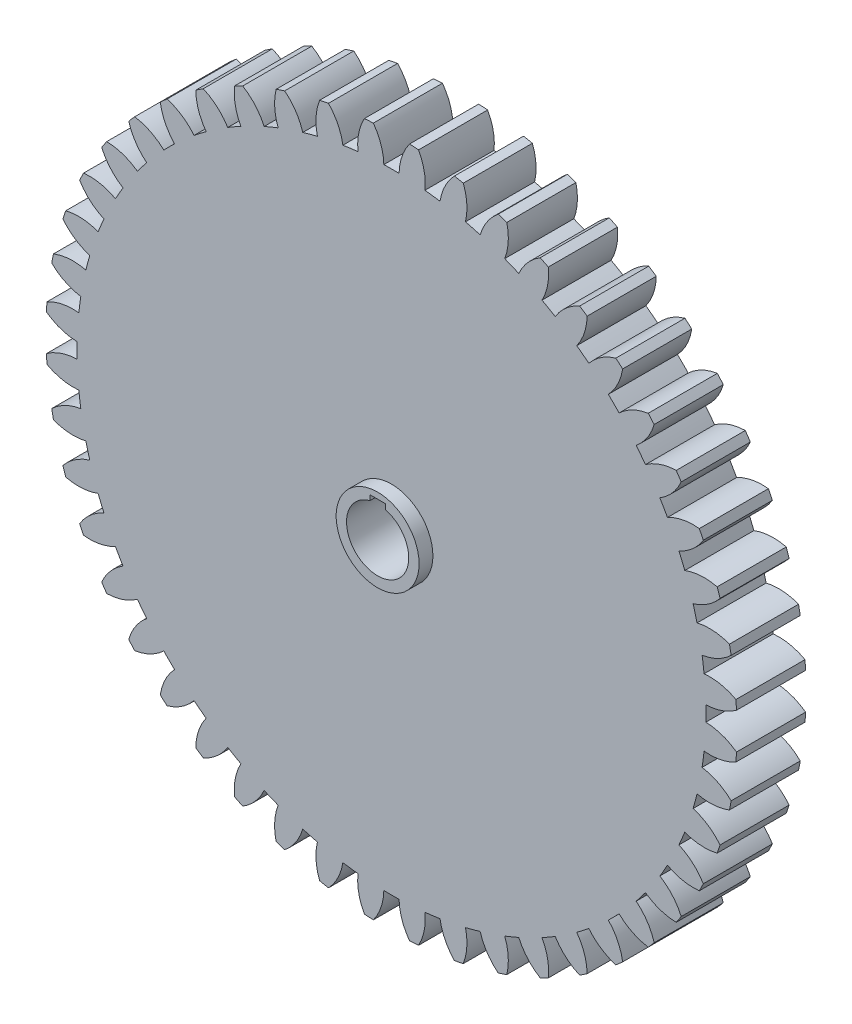
SolidWorks part; units mm, degrees
material "Plain Carbon Steel"
ref_plane "Front Plane" through (0, 0, 0) normal (0, 0, 1) x (1, 0, 0)
ref_plane "Top Plane" through (0, 0, 0) normal (0, 1, 0) x (1, 0, 0)
ref_plane "Right Plane" through (0, 0, 0) normal (1, 0, 0) x (0, 0, -1)
sketch "Sketch2" plane through (0, 0, 0) normal (0, 0, 1) x (1, 0, 0)
  circle A0 centre (0, 0) radius 50
  circle A1 centre (0, 0) radius 48 construction
  dimension "D1" = 96
  dimension "D2" = 100
extrude "Boss-Extrude1" add sketch "Sketch2" along normal mid plane 10
sketch "Sketch3" plane through (0, 0, 0) normal (0, 0, 1) x (1, 0, 0)
  line L0 (0, 50) -> (0, 0) construction
  line L1 (0, 0) -> (6.5263, 49.5722) construction
  line L2 (0, 0) -> (3.2702, 49.8929) construction
  line L3 (-1.1008, 45.4867) -> (0, 0) construction
  line L4 (-2.2887, 49.9476) -> (0, 43.6593) construction
  line L5 (-1.5705, 47.9743) -> (1.5705, 47.9743) construction
  line L6 (1.5705, 47.9743) -> (4.7048, 47.7689) construction
  circle A0 centre (0, 0) radius 46 construction
  circle A2 centre (0, 0) radius 50 construction
  arc A3 (-2.6178, 49.9314) -> (-1.1008, 45.4867) centre (-8.9254, 45.2973) cw
  arc A4 (2.6178, 49.9314) -> (1.1008, 45.4867) centre (8.9254, 45.2973) ccw
  circle A5 centre (0, 0) radius 48 construction
  arc A6 (1.1008, 45.4867) -> (-1.1008, 45.4867) centre (0, 0) ccw
  circle A7 centre (0, 0) radius 50
  arc A8 (2.6178, 49.9314) -> (-2.6178, 49.9314) centre (0, 0) ccw
  dimension "D1" = 7.5
  dimension "D4" = 20
  dimension "D3" = 0.5
  dimension "D5" = 0
extrude "Cut-Extrude1" cut sketch "Sketch3" against normal through all both and the other way through all
sketch "Sketch4" plane through (0, 0, 5) normal (0, 0, 1) x (1, 0, 0)
  line L1 (-1.125, 3.6071) -> (1.125, 3.6071)
  line L2 (-1.125, 3.6071) -> (-1.125, 5.1071)
  line L3 (-1.125, 5.1071) -> (1.125, 5.1071)
  line L4 (1.125, 3.6071) -> (1.125, 5.1071)
  arc A0 (-1.125, 4.3571) -> (1.125, 4.3571) centre (0, 0) ccw
  circle A1 centre (0, 0) radius 6
  point P8 (0, 3.6071)
  point P9 (-1.125, 4.3571)
  dimension "D1" = 12
  dimension "D2" = 9
  dimension "D3" = 2.25
  dimension "D4" = 1.5
extrude "Boss-Extrude2" add sketch "Sketch4" along normal blind 2 contours A1 A0 L2 L3 L4 region at (-5.8303, 0, 5)
mirror "Mirror1" about plane through (0, 0, 0) normal (0, 0, 1) of "Boss-Extrude2"
extrude "Cut-Extrude6" cut sketch "Sketch4<4>" against normal through all both and the other way through all contours L2 A0 L4 L1 region at (0, -0.1243, 5)
sketch "Sketch4<4>" plane through (0, 0, 5) normal (0, 0, 1) x (1, 0, 0) same geometry as "Sketch4"
pattern_circular "CirPattern1" count 48 over 360 about axis through (0, 0, -5) along (0, 0, 1) of "Cut-Extrude1"
equation "\"module\"= 2mm"
equation "\"pressure angle\"= 20"
equation "\"num of teeth\"= 48"
equation "\"D1@Sketch2\"= \"module\" * \"num of teeth\""
equation "\"D2@Sketch2\"= (\"num of teeth\"+2) * \"module\""
equation "\"D1@Sketch3\"= 360 / \"num of teeth\""
equation "\"D2@Sketch3\"= \"module\" * 2"
equation "\"D4@Sketch3\"= \"pressure angle\""
equation "\"D1@Fillet1\"= 0.3 * \"module\""
equation "\"D1@Chamfer1\"= \"module\""
equation "\"D1@CirPattern1\"=48"
equation "\"D3@Sketch4\"= 9 / 4"
equation "\"D4@Sketch4\"= 9 / 6"
